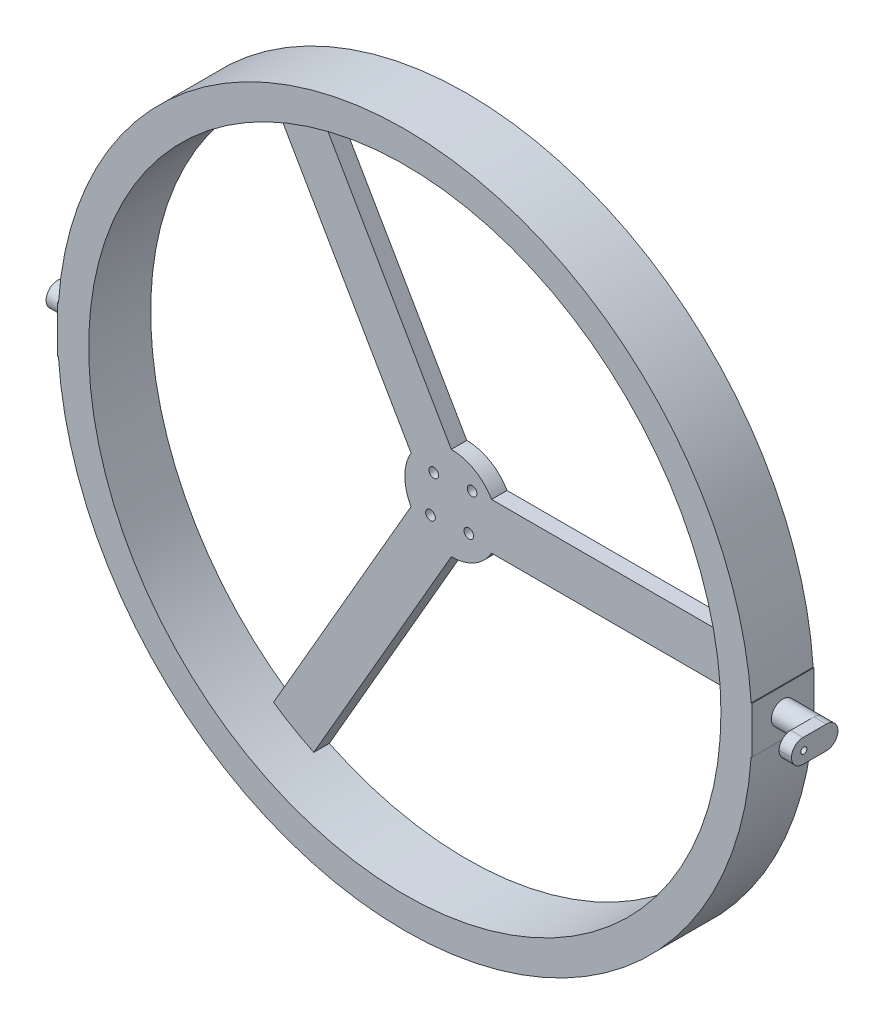
SolidWorks part; units mm, degrees
note: The reader was unsure of these and kept them because the rebuilt part matched: shared geometry of "Sketch1<3>".
ref_plane "Front Plane" through (0, 0, 0) normal (0, 0, 1) x (1, 0, 0)
ref_plane "Top Plane" through (0, 0, 0) normal (0, 1, 0) x (1, 0, 0)
ref_plane "Right Plane" through (0, 0, 0) normal (1, 0, 0) x (0, 0, -1)
sketch "Sketch1" plane through (0, 0, 0) normal (0, 0, 1) x (1, 0, 0)
  line L0 (12.9904, -7.5) -> (101.7239, -7.5)
  line L1 (12.9904, 7.5) -> (101.7239, 7.5)
  line L2 (0, 15) -> (-44.3668, 91.8455)
  line L3 (-12.9904, 7.5) -> (-57.3571, 84.3455)
  line L4 (0, -15) -> (-44.3668, -91.8455)
  line L5 (-12.9904, -7.5) -> (-57.3571, -84.3455)
  line L6 (111.7486, 7.5) -> (112, 7.5)
  line L7 (112, 7.5) -> (112, -7.5)
  line L8 (112, -7.5) -> (111.7486, -7.5)
  line L9 (-111.7486, 7.5) -> (-112, 7.5)
  line L10 (-112, 7.5) -> (-112, -7.5)
  line L11 (-112, -7.5) -> (-111.7486, -7.5)
  circle A0 centre (0, 0) radius 102
  arc A1 (111.7778, -7.0515) -> (111.7939, -6.7907) centre (0, 0) ccw
  circle A2 centre (0, 0) radius 15
  arc A4 (111.7549, 7.406) -> (-111.751, 7.4635) centre (0, 0) ccw
  arc A5 (-111.751, 7.4635) -> (-111.768, 7.2051) centre (0, 0) ccw
  arc A6 (-111.7531, -7.433) -> (111.7778, -7.0515) centre (0, 0) ccw
  point P23 (106.25, 6.25)
  point P27 (-112.5, -6.25)
  dimension "D1" = 204
  dimension "D2" = 10
  dimension "D3" = 30
  dimension "D5" = 7.5
  dimension "D4" = 15
  dimension "D6" = 15
  dimension "D7" = 7.5
  dimension "D8" = 15
  dimension "D9" = 7.5
  dimension "D10" = 120
  dimension "D11" = 120
  dimension "D12" = 112
  dimension "D13" = 15
  dimension "D14" = 0
  dimension "D15" = 112
extrude "Boss-Extrude1" add sketch "Sketch1" along normal blind 20 contours A1 A0
extrude "Boss-Extrude2" add sketch "Sketch1<3>" along normal blind 5 contours A2 L2 A0 L3 | A2 | A2 L5 A0 L4 | A2 L0 A0 L1
sketch "Sketch1<3>" plane through (0, 0, 0) normal (0, 0, 1) x (1, 0, 0) same geometry as "Sketch1"
sketch "Sketch2" plane through (0, 0, 5) normal (0, 0, 1) x (1, 0, 0)
  circle A0 centre (-5.6569, 5.6569) radius 1.55
  circle A1 centre (6.7175, 6.7175) radius 1.55
  circle A2 centre (5.6569, -5.6569) radius 1.55
  circle A3 centre (-6.7175, -6.7175) radius 1.55
  point P8 (0, 0)
  dimension "D1" = 3.1
  dimension "D2" = 3.1
  dimension "D3" = 3.1
  dimension "D4" = 3.1
  dimension "D5" = 19
  dimension "D6" = 16
  dimension "D7" = 9.5
  dimension "D8" = 8
extrude "Cut-Extrude1" cut sketch "Sketch2" against normal blind 5
sketch "Sketch3" plane through (112, 0, 0) normal (1, 0, 0) x (0, 0, -1)
  line L0 (-20, 7.5) -> (-20, -7.5) construction
  circle A0 centre (-10, 0) radius 3.75
  dimension "D1" = 7.5
  dimension "D2" = 10
sketch "Sketch4" plane through (-112, 0, 0) normal (-1, 0, 0) x (0, 0, 1)
  line L0 (20, 7.5) -> (20, -7.5) construction
  circle A0 centre (10, 0) radius 3.75
  dimension "D1" = 7.5
  dimension "D2" = 10
extrude "Boss-Extrude3" add sketch "Sketch4" along normal blind 10
extrude "Boss-Extrude4" add sketch "Sketch3" along normal blind 10
sketch "Sketch5" plane through (122, 0, 0) normal (1, 0, 0) x (0, 0, -1)
  line L1 (-6.25, 3.75) -> (-21.25, 3.75)
  line L2 (-6.25, 3.75) -> (-6.25, -3.75)
  line L3 (-6.25, -3.75) -> (-21.25, -3.75)
  line L4 (-21.25, 3.75) -> (-21.25, -3.75)
  circle A1 centre (-10, 0) radius 3.75 construction
  dimension "D1" = 7.5
  dimension "D2" = 3.75
  dimension "D3" = 3.75
  dimension "D4" = 15
extrude "Boss-Extrude5" add sketch "Sketch5" along normal blind 4
fillet "Fillet2" radius 3.75 4 edges at (124, -3.75, 21.25) (124, 3.75, 21.25) (124, 3.75, 6.25) (124, -3.75, 6.25)
sketch "Sketch6" plane through (126, 0, 0) normal (1, 0, 0) x (0, 0, -1)
  circle A0 centre (-17.25, 0) radius 1
  dimension "D1" = 2
  dimension "D2" = 4
extrude "Cut-Extrude2" cut sketch "Sketch6" against normal blind 4
